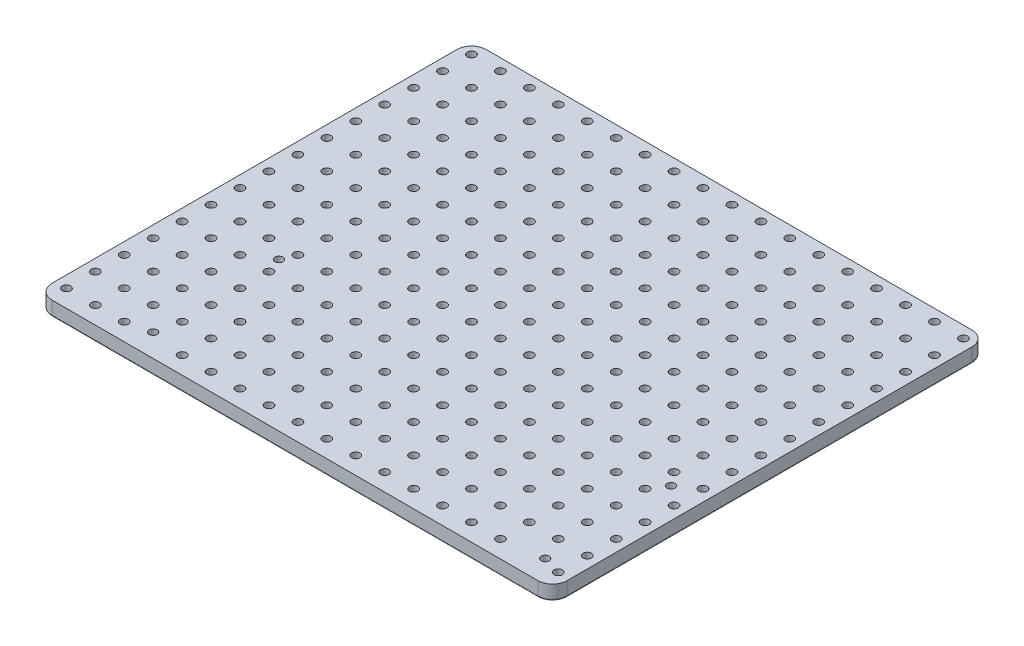
SolidWorks part; units mm, degrees
ref_plane "Front Plane" through (0, 0, 0) normal (0, 0, 1) x (1, 0, 0)
ref_plane "Top Plane" through (0, 0, 0) normal (0, 1, 0) x (1, 0, 0)
ref_plane "Right Plane" through (0, 0, 0) normal (1, 0, 0) x (0, 0, -1)
sketch "Sketch1" plane through (0, 0, 0) normal (0, 1, 0) x (1, 0, 0)
  line L1 (0, 0) -> (178, 0)
  line L2 (0, 0) -> (0, 150)
  line L3 (0, 150) -> (178, 150)
  line L4 (178, 0) -> (178, 150)
  dimension "D1" = 178
  dimension "D2" = 150
extrude "Boss-Extrude1" add sketch "Sketch1" along normal blind 5
sketch "Sketch2" plane through (0, 5, 0) normal (0, 1, 0) x (1, 0, 0)
  line L0 (178, 150) -> (0, 150) construction
  line L1 (0, 150) -> (0, 0) construction
  circle A0 centre (4, 146) radius 1.45
  dimension "D1" = 2.9
  dimension "D2" = 4
  dimension "D3" = 4
extrude "Cut-Extrude1" cut sketch "Sketch2" against normal through all
pattern_linear "LPattern1" count 18 spacing 10 along (1, 0, 0) count 15 spacing 10 along (0, 0, 1) skipping (3, 14), (16, 14) of "Cut-Extrude1"
sketch "Sketch3" plane through (0, 0, 0) normal (0, -1, 0) x (1, 0, 0)
  circle A0 centre (167.5885, -7.8758) radius 1.7 construction
  circle A1 centre (167.5885, -51.3758) radius 1.7 construction
  circle A2 centre (32.0885, -51.3758) radius 1.7 construction
  circle A3 centre (32.0885, -7.8758) radius 1.7 construction
  circle A4 centre (167.5885, -7.8758) radius 1.7 construction
  circle A5 centre (167.5885, -51.3758) radius 1.7 construction
  circle A6 centre (32.0885, -51.3758) radius 1.7 construction
  circle A7 centre (32.0885, -7.8758) radius 1.7 construction
  circle A8 centre (32.0885, -7.8758) radius 1.4
  circle A9 centre (32.0885, -51.3758) radius 1.4
  circle A10 centre (167.5885, -51.3758) radius 1.4
  circle A11 centre (167.5885, -7.8758) radius 1.4
  dimension "D1" = 2.8
extrude "Cut-Extrude2" cut sketch "Sketch3" against normal through all
fillet "Fillet1" radius 5 4 edges at (0, 2.5, -150) (178, 2.5, -150) (178, 2.5, 0) (0, 2.5, 0)
fillet "Fillet2" radius 0.5 58 edges at (134, 0, -4.55) (54, 0, -4.55) (14, 0, -4.55) (164, 0, -14.55) (84, 0, -14.55) (54, 0, -14.55) (34, 0, -14.55) (4, 0, -14.55) (74, 0, -24.55) (34, 0, -24.55) (4, 0, -24.55) (174, 0, -34.55) (164, 0, -34.55) (154, 0, -34.55) (124, 0, -34.55) (94, 0, -34.55) (84, 0, -34.55) (14, 0, -34.55) (104, 0, -44.55) (54, 0, -44.55) (14, 0, -44.55) (124, 0, -54.55) (104, 0, -54.55) (44, 0, -54.55) (174, 0, -64.55) (114, 0, -64.55) (124, 0, -74.55) (94, 0, -74.55) (84, 0, -74.55) (74, 0, -74.55) (64, 0, -74.55) (44, 0, -74.55) (74, 0, -84.55) (54, 0, -84.55) (14, 0, -84.55) (174, 0, -94.55) (124, 0, -94.55) (114, 0, -94.55) (94, 0, -94.55) (24, 0, -94.55) (174, 0, -104.55) (124, 0, -104.55) (34, 0, -104.55) (124, 0, -114.55) (94, 0, -114.55) (64, 0, -114.55) (54, 0, -114.55) (34, 0, -114.55) (174, 0, -124.55) (54, 0, -124.55) (114, 0, -134.55) (24, 0, -134.55) (14, 0, -134.55) (124, 0, -144.55) (34, 0, -144.55) (176.5355, 0, -1.4645) (178, 0, -75) (89, 0, -150)
